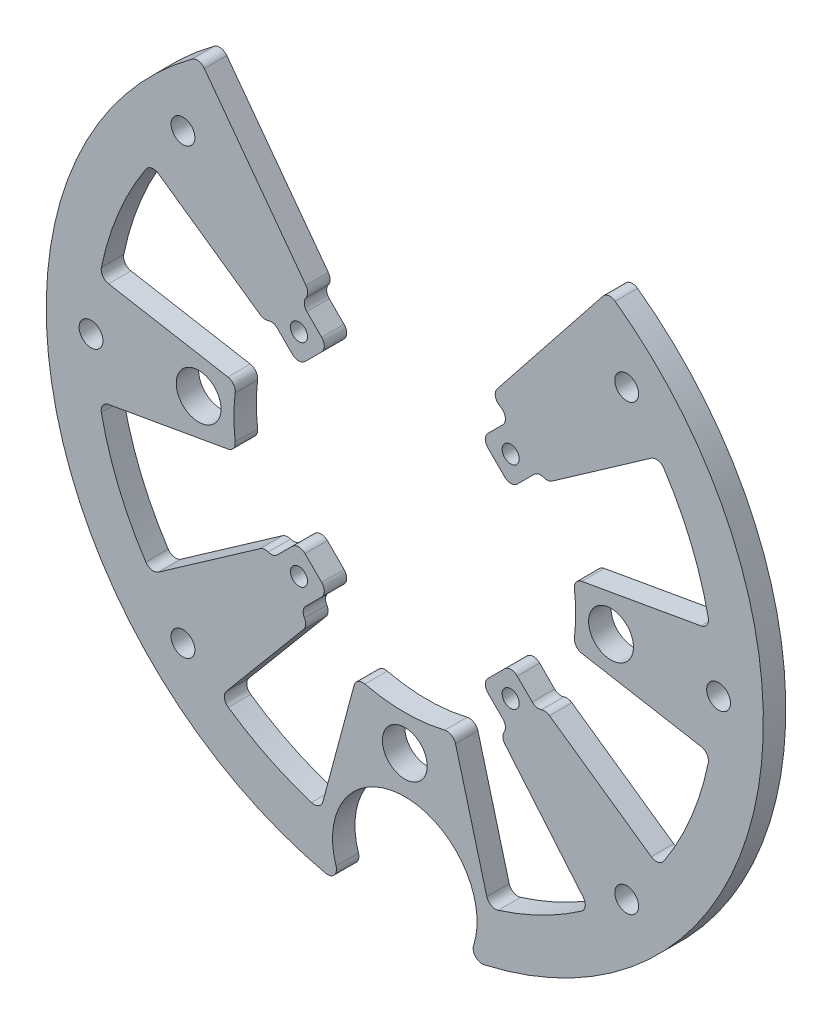
SolidWorks part; units mm, degrees
ref_plane "Front Plane" through (0, 0, 0) normal (0, 0, 1) x (1, 0, 0)
ref_plane "Top Plane" through (0, 0, 0) normal (0, 1, 0) x (1, 0, 0)
ref_plane "Right Plane" through (0, 0, 0) normal (1, 0, 0) x (0, 0, -1)
sketch "Sketch1" plane through (0, 0, 0) normal (0, 0, 1) x (1, 0, 0)
  circle A0 centre (0, 0) radius 48.4359
  circle A1 centre (0, 0) radius 101.6
extrude "Extrude1" add sketch "Sketch1" along normal blind 6.35
sketch "Sketch4" plane through (0, 0, 6.35) normal (0, 0, 1) x (1, 0, 0)
  point P0 (62.8618, -62.8618)
  point P1 (88.9, 0)
  point P2 (62.8618, 62.8618)
  point P3 (-62.8618, 62.8618)
  point P4 (-88.9, 0)
  point P5 (-62.8618, -62.8618)
hole_wizard "1/4 Clearance Hole1" positions "Sketch9" profile "Sketch8" hole size "1/4" standard "Ansi Inch" end condition through all
sketch "Sketch9" plane through (0, 0, 6.35) normal (0, 0, 1) x (1, 0, 0)
  point P1 (62.8618, -62.8618)
  point P3 (88.9, 0)
  point P5 (62.8618, 62.8618)
  point P7 (-62.8618, 62.8618)
  point P9 (-88.9, 0)
  point P11 (-62.8618, -62.8618)
sketch "Sketch8" plane through (62.8618, -62.8618, 6.35) normal (1, 0, 0) x (0, -1, 0)
  line L0 (0, 0) -> (0, 6.35)
  line L1 (0, 6.35) -> (3.3782, 6.35)
  line L2 (3.3782, 6.35) -> (3.3782, 0)
  line L5 (3.3782, 0) -> (0, 0)
  line L11 (0, -6.35) -> (0, 107.95) construction
  dimension "Thru Hole Dia." = 6.7564
  dimension "Thru Hole Depth" = 6.35
sketch "Sketch11" plane through (0, 0, 6.35) normal (0, 0, 1) x (1, 0, 0)
  circle A0 centre (0, -89.535) radius 20.4787
extrude "Cut-Extrude1" cut sketch "Sketch11" against normal through all
sketch "Sketch12" plane through (0, 0, 6.35) normal (0, 0, 1) x (1, 0, 0)
  circle A0 centre (0, -58.42) radius 6.35
  circle A1 centre (-58.42, 0) radius 6.35
  circle A2 centre (58.42, 0) radius 6.35
  dimension "D1" = 12.7
extrude "Cut-Extrude2" cut sketch "Sketch12" against normal through all
sketch "Sketch13" plane through (0, 0, 6.35) normal (0, 0, 1) x (1, 0, 0)
  line L0 (0, 0) -> (0, -67.9248) construction
  line L1 (0, 0) -> (61.5438, 0) construction
  line L2 (0, 0) -> (29.9999, -29.9999) construction
  line L3 (30.0672, -21.7618) -> (44.904, -36.5986)
  line L4 (44.904, -36.5986) -> (36.5986, -44.904)
  line L5 (30.0672, -21.7618) -> (21.7618, -30.0672)
  line L6 (21.7618, -30.0672) -> (36.5986, -44.904)
  line L7 (-30.0672, -21.7618) -> (-44.904, -36.5986)
  line L8 (-30.0672, -21.7618) -> (-21.7618, -30.0672)
  line L9 (-21.7618, -30.0672) -> (-36.5986, -44.904)
  line L10 (-44.904, -36.5986) -> (-36.5986, -44.904)
  line L11 (-30.0672, 21.7618) -> (-21.7618, 30.0672)
  line L12 (-30.0672, 21.7618) -> (-44.904, 36.5986)
  line L13 (-44.904, 36.5986) -> (-36.5986, 44.904)
  line L14 (-21.7618, 30.0672) -> (-36.5986, 44.904)
  line L15 (30.0672, 21.7618) -> (21.7618, 30.0672)
  line L16 (30.0672, 21.7618) -> (44.904, 36.5986)
  line L17 (21.7618, 30.0672) -> (36.5986, 44.904)
  line L18 (44.904, 36.5986) -> (36.5986, 44.904)
  circle A0 centre (-29.9999, 29.9999) radius 2.4265
  circle A1 centre (29.9999, 29.9999) radius 2.4265
  circle A2 centre (-29.9999, -29.9999) radius 2.4265
  circle A3 centre (29.9999, -29.9999) radius 2.4265
  point P11 (25.9145, -25.9145)
  point P12 (40.7513, -40.7513)
extrude "Extrude2" add sketch "Sketch13" against normal up to surface (6.35 mm away) up to face at (64.77, 0, 0)
sketch "Sketch14" plane through (0, 0, 6.35) normal (0, 0, 1) x (1, 0, 0)
  line L0 (0, -7.6401) -> (0, -64.3895) construction
  line L1 (0, 0) -> (76.0963, 0) construction
  line L2 (12.0286, 26.2847) -> (72.4862, 102.3885)
  line L3 (72.4862, 102.3885) -> (0, 148.4755)
  line L4 (-72.4862, 102.3885) -> (0, 148.4755)
  line L5 (-14.9526, 24.7385) -> (-72.4862, 102.3885)
  line L6 (8.6526, -27.5809) -> (23.9004, -84.4864)
  line L7 (14.2276, -25.1624) -> (52.2951, -70.5294)
  line L8 (-71.9231, 50.3611) -> (-23.6786, 16.5799)
  line L9 (-86.468, 15.2466) -> (-28.4671, 5.0195)
  line L10 (-8.6522, -27.581) -> (-23.9004, -84.4864)
  line L11 (-14.2295, -25.1613) -> (-52.2951, -70.5294)
  line L12 (-86.468, -15.2466) -> (-28.4671, -5.0195)
  line L13 (-71.9231, -50.3611) -> (-23.6786, -16.5799)
  line L14 (23.6786, -16.5799) -> (71.9231, -50.3611)
  line L15 (28.4671, -5.0195) -> (86.468, -15.2466)
  line L16 (28.4671, 5.0195) -> (86.468, 15.2466)
  line L17 (23.6786, 16.5799) -> (71.9231, 50.3611)
  arc A0 (23.9004, -84.4864) -> (52.2951, -70.5294) centre (0, 0) ccw
  arc A1 (-52.2951, -70.5294) -> (-23.9004, -84.4864) centre (0, 0) ccw
  arc A2 (-86.468, -15.2466) -> (-71.9231, -50.3611) centre (0, 0) ccw
  arc A3 (-71.9231, 50.3611) -> (-86.468, 15.2466) centre (0, 0) ccw
  arc A4 (86.468, 15.2466) -> (71.9231, 50.3611) centre (0, 0) ccw
  arc A5 (71.9231, -50.3611) -> (86.468, -15.2466) centre (0, 0) ccw
  arc A6 (12.0286, 26.2847) -> (-14.9526, 24.7385) centre (0, 0) ccw
  arc A7 (28.4671, 5.0195) -> (23.6786, 16.5799) centre (0, 0) ccw
  arc A8 (23.6786, -16.5799) -> (28.4671, -5.0195) centre (0, 0) ccw
  arc A9 (8.6526, -27.5809) -> (14.2276, -25.1624) centre (0, 0) ccw
  arc A10 (-14.2295, -25.1613) -> (-8.6522, -27.581) centre (0, 0) ccw
  arc A11 (-28.4671, -5.0195) -> (-23.6786, -16.5799) centre (0, 0) ccw
  arc A12 (-23.6786, 16.5799) -> (-28.4671, 5.0195) centre (0, 0) ccw
  dimension "D5" = 75
  dimension "D1" = 10
  dimension "D2" = 15
  dimension "D3" = 25
  dimension "D4" = 25
extrude "Cut-Extrude3" cut sketch "Sketch14" against normal blind 6.35
fillet "Fillet1" radius 2.54 23 edges at (47.7, -8.4108, 3.175) (29.8439, -38.1494, 3.175) (-58.2836, 83.2201, 3.175) (-30.0672, -21.7618, 3.175) (-30.0672, 21.7618, 3.175) (30.0672, 21.7618, 3.175) (-21.7618, -30.0672, 3.175) (-21.7618, 30.0672, 3.175) (21.7618, -30.0672, 3.175) (30.0672, -21.7618, 3.175) (21.7618, 30.0672, 3.175) (86.468, 15.2466, 3.175) (71.9231, 50.3611, 3.175) (-86.468, -15.2466, 3.175) (23.9004, -84.4864, 3.175) (52.2951, -70.5294, 3.175) (-71.9231, 50.3611, 3.175) (86.468, -15.2466, 3.175) (-71.9231, -50.3611, 3.175) (71.9231, -50.3611, 3.175) (-23.9004, -84.4864, 3.175) (-52.2951, -70.5294, 3.175) (-86.468, 15.2466, 3.175)
fillet "Fillet2" radius 2.54 2 edges at (-38.1494, -29.8439, 3.175) (39.6763, 27.7817, 3.175)
fillet "Fillet3" radius 2.54 4 edges at (38.1494, -29.8439, 3.175) (26.9079, -40.2741, 3.175) (13.71, -46.455, 3.175) (-29.8439, 38.1494, 3.175)
fillet "Fillet4" radius 2.54 8 edges at (-38.1494, 29.8439, 3.175) (-47.7, -8.4108, 3.175) (17.5605, -100.0709, 3.175) (24.3909, 41.8464, 3.175) (-26.6098, 40.4716, 3.175) (47.7, 8.4108, 3.175) (39.6763, -27.7817, 3.175) (57.623, 83.6788, 3.175)
fillet "Fillet5" radius 2.54 5 edges at (-39.6763, 27.7817, 3.175) (-47.7, 8.4108, 3.175) (-26.9091, -40.2733, 3.175) (-17.5605, -100.0709, 3.175) (-13.7096, -46.4551, 3.175)
fillet "Fillet6" radius 2.54 4 edges at (-29.8439, -38.1494, 3.175) (-39.6763, -27.7817, 3.175) (38.1494, 29.8439, 3.175) (29.8439, 38.1494, 3.175)
